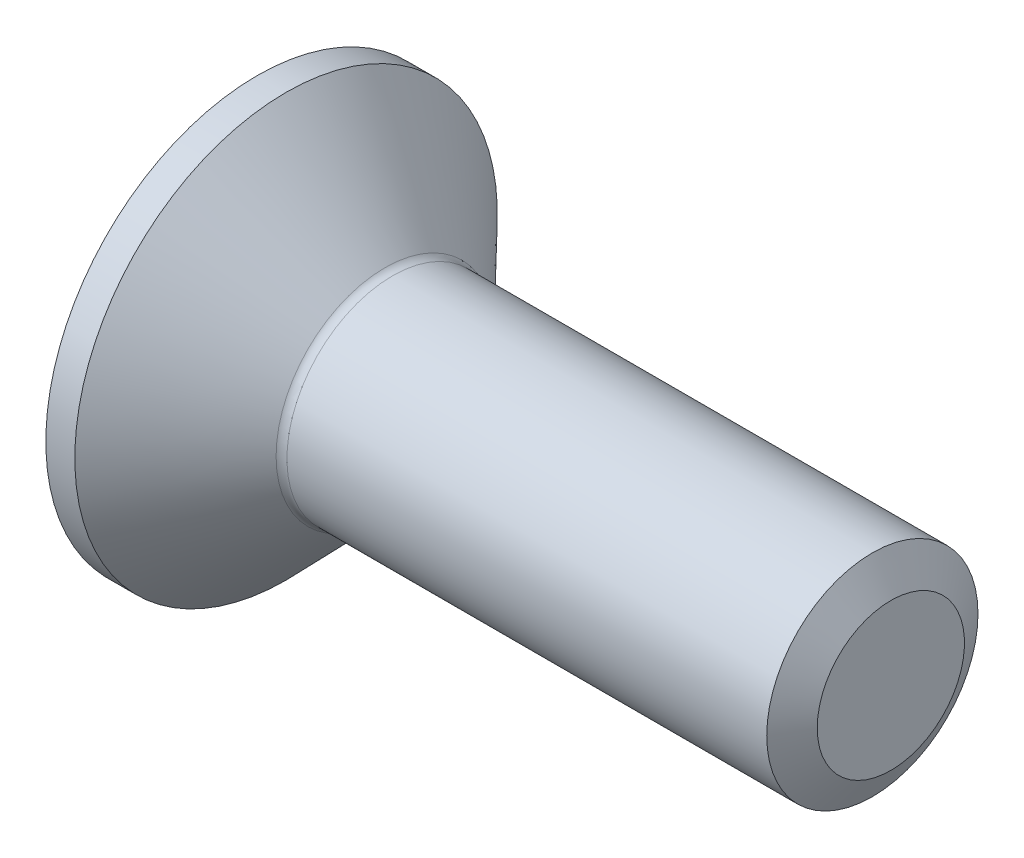
SolidWorks part; units mm, degrees
material "8.8级"
ref_plane "前视基准面" through (0, 0, 0) normal (0, 0, 1) x (1, 0, 0)
ref_plane "上视基准面" through (0, 0, 0) normal (0, 1, 0) x (1, 0, 0)
ref_plane "右视基准面" through (0, 0, 0) normal (1, 0, 0) x (0, 0, -1)
sketch "草图1" plane through (0, 0, 0) normal (0, 0, 1) x (1, 0, 0)
  line L0 (0, 2) -> (-9.4351, 2)
  line L1 (-9.579, 2.0611) -> (-11.4514, 4)
  line L2 (-11.4514, 4) -> (-12, 4)
  line L3 (-12, 4) -> (-12, 0)
  line L4 (-12, 0) -> (0, 0)
  line L5 (0, 0) -> (0, 2)
  line L6 (0, 0) -> (-12, 0) construction
  arc A0 (-9.4351, 2) -> (-9.579, 2.0611) centre (-9.4351, 2.2) cw
  point P9 (-9.52, 2)
  dimension "r" = 0.2
  dimension "k" = 2.48
  dimension "dk" = 8
  dimension "l" = 12
  dimension "d" = 4
  dimension "D5" = 46
revolve "旋转1" add sketch "草图1" angle 360 about L6
cosmetic thread "装饰螺纹线1" parameters "b"=8, "D2"=3.44
sketch "草图2" plane through (-12, 0, 0) normal (-1, 0, 0) x (0, 0, 1)
  line L1 (0, 1.4434) -> (-1.25, 0.7217)
  line L2 (-1.25, 0.7217) -> (-1.25, -0.7217)
  line L3 (-1.25, -0.7217) -> (0, -1.4434)
  line L4 (0, -1.4434) -> (1.25, -0.7217)
  line L5 (1.25, -0.7217) -> (1.25, 0.7217)
  line L6 (1.25, 0.7217) -> (0, 1.4434)
  circle A0 centre (0, 0) radius 1.25 construction
  dimension "s" = 2.5
extrude "切除-拉伸1" cut sketch "草图2" against normal blind 2.58
sketch "草图6" plane through (0, 0, 0) normal (0, 0, 1) x (1, 0, 0)
  line L0 (-10.5, 1.4434) -> (-9.6667, 0)
  line L1 (-9.6667, 0) -> (-9.05, 0)
  line L2 (-9.05, 0) -> (-9.05, 1.4434)
  line L3 (-9.05, 1.4434) -> (-10.5, 1.4434)
  line L4 (-12, 0) -> (-9.42, 0) construction
  line L5 (-12, 0) -> (-14.87, 0) construction
  dimension "t" = 1.5
  dimension "D1" = 60
  dimension "t1" = 2.58
  dimension "e-s" = 0.37
  dimension "e" = 2.87
revolve "旋转2" add sketch "草图6" angle 360 about L4
sketch "草图7" plane through (0, 0, 0) normal (0, 0, 1) x (1, 0, 0)
  line L0 (-12, 1.4434) -> (-12, 0)
  line L1 (-12, 0) -> (-11.593, 0)
  line L2 (-11.593, 0) -> (-12, 1.4434)
  line L3 (-12, 0) -> (-11.593, 0) construction
  dimension "e-s*1.1" = 0.407
revolve "切除-旋转2" cut sketch "草图7" angle 360 about L3
sketch "草图4" plane through (0, 0, 0) normal (0, 0, 1) x (1, 0, 0)
  line L0 (-0.35, 2) -> (0, 1.3938)
  line L1 (0, -2) -> (0, 2) construction
  line L2 (0, 1.3938) -> (0.35, 2)
  line L3 (0.35, 2) -> (-0.35, 2)
  line L4 (-0.35, 0) -> (0.35, 0) construction
  dimension "d" = 4
  dimension "p" = 0.7
revolve "切除-旋转1" cut sketch "草图4" angle 360 about L4
ref_axis "基准轴1" through (-21.1715, 0, 0) along (1, 0, 0)
pattern_linear "阵列(线性)2" [suppressed] count 11 spacing 0.7 along (-1, 0, 0) of bodies 104
equation "\"D2@装饰螺纹线1\" = \"d@草图1\" * 0.86"
equation "\"e-s@草图6\" = \"e@草图6\" - \"s@草图2\""
equation "\"t1@切除-拉伸1\" = \"k@草图1\" + 0.1"
equation "\"t1@草图6\" = \"t1@切除-拉伸1\""
equation "\"e-s*1.1@草图7\" = \"e-s@草图6\" * 1.1"
equation "\"d@草图4\" = \"d@草图1\""
equation "\"D3@阵列(线性)2\" = \"p@草图4\""
equation "\"D1@阵列(线性)2\" = \"b@装饰螺纹线1\" / \"p@草图4\""
